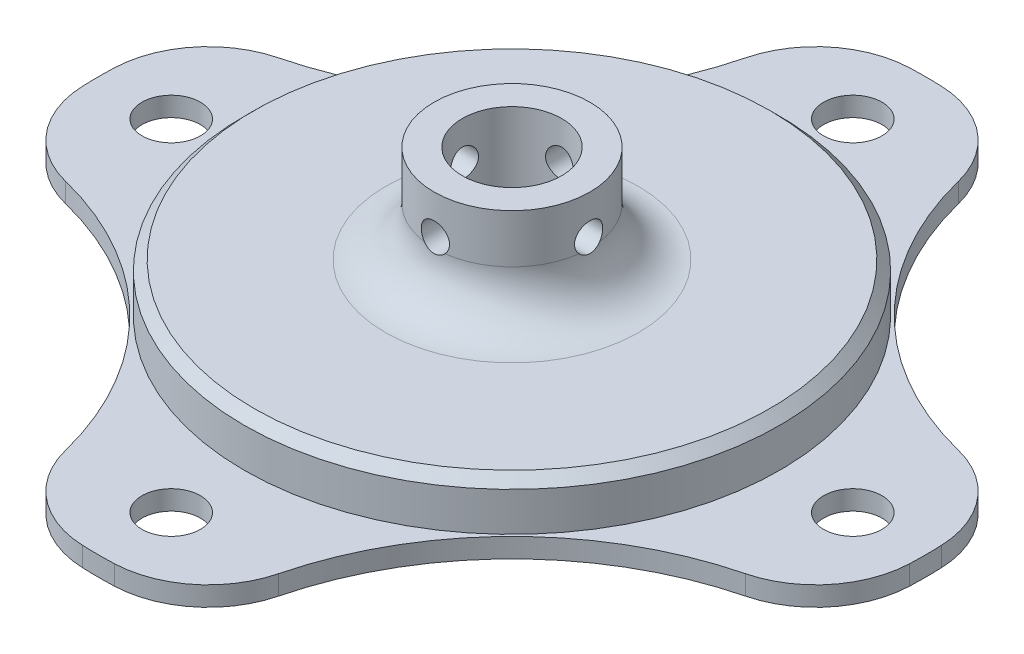
SolidWorks part; units mm, degrees
ref_plane "Front Plane" through (0, 0, 0) normal (0, 0, 1) x (1, 0, 0)
ref_plane "Top Plane" through (0, 0, 0) normal (0, 1, 0) x (1, 0, 0)
ref_plane "Right Plane" through (0, 0, 0) normal (1, 0, 0) x (0, 0, -1)
sketch "Sketch1" plane through (0, 0, 0) normal (0, 1, 0) x (1, 0, 0)
  circle A0 centre (0, 0) radius 27.5
  dimension "D1" = 55
extrude "Boss-Extrude1" add sketch "Sketch1" against normal blind 5
sketch "Sketch2" plane through (0, -5, 0) normal (0, -1, 0) x (1, 0, 0)
  circle A0 centre (0, 0) radius 42.5
  dimension "D1" = 85
extrude "Boss-Extrude2" add sketch "Sketch2" along normal blind 2
sketch "Sketch3" plane through (0, -5, 0) normal (0, 1, 0) x (1, 0, 0)
  circle A0 centre (0, 35) radius 3
  circle A1 centre (35, 0) radius 3
  circle A2 centre (0, -35) radius 3
  circle A3 centre (-35, 0) radius 3
  circle A4 centre (0, 0) radius 42.5 construction
  arc A5 (-10, 41.3068) -> (-41.3068, 10) centre (-42.9586, 42.9586) cw
  arc A6 (41.3068, 10) -> (10, 41.3068) centre (42.9586, 42.9586) cw
  arc A7 (10, -41.3068) -> (41.3068, -10) centre (42.9586, -42.9586) cw
  arc A8 (-41.3068, -10) -> (-10, -41.3068) centre (-42.9586, -42.9586) cw
  circle A10 centre (0, 0) radius 42.5
  circle A11 centre (0, 0) radius 42.5
  point P12 (0, 0)
  point P27 (0, 0)
  circle M3 centre (0, 0) radius 42.5
  dimension "D1" = 6
  dimension "D6" = 33
  dimension "D2" = 35
  dimension "D3" = 4
  dimension "D4" = 10
  dimension "D5" = 10
  dimension "D8" = 0
  dimension "D7" = 4
extrude "Cut-Extrude1" cut sketch "Sketch3" against normal blind 2 contours A5 M3 | A0 | A6 M3 | A1 | A2 | A7 M3 | A8 M3 | A3 region at (0, -5, -35) region at (35, -5, 0) region at (0, -5, 35) region at (-35, -5, 0) region at (-24.9758, -5, -24.9758) region at (24.9758, -5, -24.9758) region at (-24.9758, -5, 24.9758) region at (24.9758, -5, 24.9758)
sketch "Sketch4" plane through (0, 0, 0) normal (0, 1, 0) x (1, 0, 0)
  circle A0 centre (0, 0) radius 11.6
  circle A1 centre (0, 23.5) radius 2.5
  circle A2 centre (20.3516, 11.75) radius 2.5
  circle A3 centre (20.3516, -11.75) radius 2.5
  circle A4 centre (0, -23.5) radius 2.5
  circle A5 centre (-20.3516, -11.75) radius 2.5
  circle A6 centre (-20.3516, 11.75) radius 2.5
  point P18 (0, 0)
  dimension "D1" = 23.2
  dimension "D2" = 5
  dimension "D3" = 23.5
  dimension "D4" = 6
extrude "Cut-Extrude2" [suppressed] cut sketch "Sketch4" against normal through all
sketch "Sketch5" plane through (0, 0, 0) normal (0, 1, 0) x (1, 0, 0)
  line L0 (-17.6947, 16.2142) -> (-10.3219, 9.4583)
  line L1 (-5.1946, 23.4311) -> (-3.0302, 13.6681)
  line L2 (0, 23.537) -> (0, 0) construction
  line L3 (17.6947, 16.2142) -> (10.3219, 9.4583)
  line L4 (5.1946, 23.4311) -> (3.0302, 13.6681)
  line L5 (22.8892, -7.2169) -> (13.352, -4.2099)
  line L6 (22.8892, 7.2169) -> (13.352, 4.2099)
  line L7 (5.1946, -23.4311) -> (3.0302, -13.6681)
  line L8 (17.6947, -16.2142) -> (10.3219, -9.4583)
  line L9 (-17.6947, -16.2142) -> (-10.3219, -9.4583)
  line L10 (-5.1946, -23.4311) -> (-3.0302, -13.6681)
  line L11 (-22.8892, 7.2169) -> (-13.352, 4.2099)
  line L12 (-22.8892, -7.2169) -> (-13.352, -4.2099)
  arc A0 (-10.3219, 9.4583) -> (-3.0302, 13.6681) centre (0, 0) cw
  arc A1 (-17.6947, 16.2142) -> (-5.1946, 23.4311) centre (0, 0) cw
  arc A2 (5.1946, 23.4311) -> (17.6947, 16.2142) centre (0, 0) cw
  arc A3 (3.0302, 13.6681) -> (10.3219, 9.4583) centre (0, 0) cw
  arc A4 (22.8892, 7.2169) -> (22.8892, -7.2169) centre (0, 0) cw
  arc A5 (13.352, 4.2099) -> (13.352, -4.2099) centre (0, 0) cw
  arc A6 (17.6947, -16.2142) -> (5.1946, -23.4311) centre (0, 0) cw
  arc A7 (10.3219, -9.4583) -> (3.0302, -13.6681) centre (0, 0) cw
  arc A8 (-5.1946, -23.4311) -> (-17.6947, -16.2142) centre (0, 0) cw
  arc A9 (-3.0302, -13.6681) -> (-10.3219, -9.4583) centre (0, 0) cw
  arc A10 (-22.8892, -7.2169) -> (-22.8892, 7.2169) centre (0, 0) cw
  arc A11 (-13.352, -4.2099) -> (-13.352, 4.2099) centre (0, 0) cw
  point P30 (0, 0)
  dimension "D2" = 14
  dimension "D3" = 35
  dimension "D4" = 12.5
  dimension "D1" = 10
  dimension "D5" = 6
extrude "Cut-Extrude3" [suppressed] cut sketch "Sketch5" against normal through all
fillet "Fillet1" radius 10 8 edges at (10, -6, -41.3068) (-10, -6, -41.3068) (-41.3068, -6, -10) (-41.3068, -6, 10) (10, -6, 41.3068) (-10, -6, 41.3068) (41.3068, -6, 10) (41.3068, -6, -10)
sketch "Sketch6" plane through (0, 0, 0) normal (0, 1, 0) x (1, 0, 0)
  circle A0 centre (0, 0) radius 8
  dimension "D1" = 16
extrude "Boss-Extrude3" add sketch "Sketch6" along normal blind 10
fillet "Fillet2" radius 5 1 edges at (0, 0, 8)
sketch "Sketch7" plane through (0, 10, 0) normal (0, 1, 0) x (1, 0, 0)
  circle A0 centre (0, 0) radius 5.1
  dimension "D1" = 10.2
extrude "Cut-Extrude4" cut sketch "Sketch7" against normal blind 20
sketch "Sketch10" plane through (0, 0, 0) normal (0, 0, 1) x (1, 0, 0)
  circle A0 centre (0, 6) radius 1.45
  point P2 (0, 0)
  dimension "D1" = 2.9
  dimension "D2" = 6
extrude "Cut-Extrude5" cut sketch "Sketch10" along normal through all both and the other way through all
pattern_circular "CirPattern1" count 4 over 360 about axis through (0, 10, 0) along (0, -1, 0) of "Cut-Extrude5"
chamfer "Chamfer1" distance 1 angle 45 1 edges at (0, 0, 27.5)
